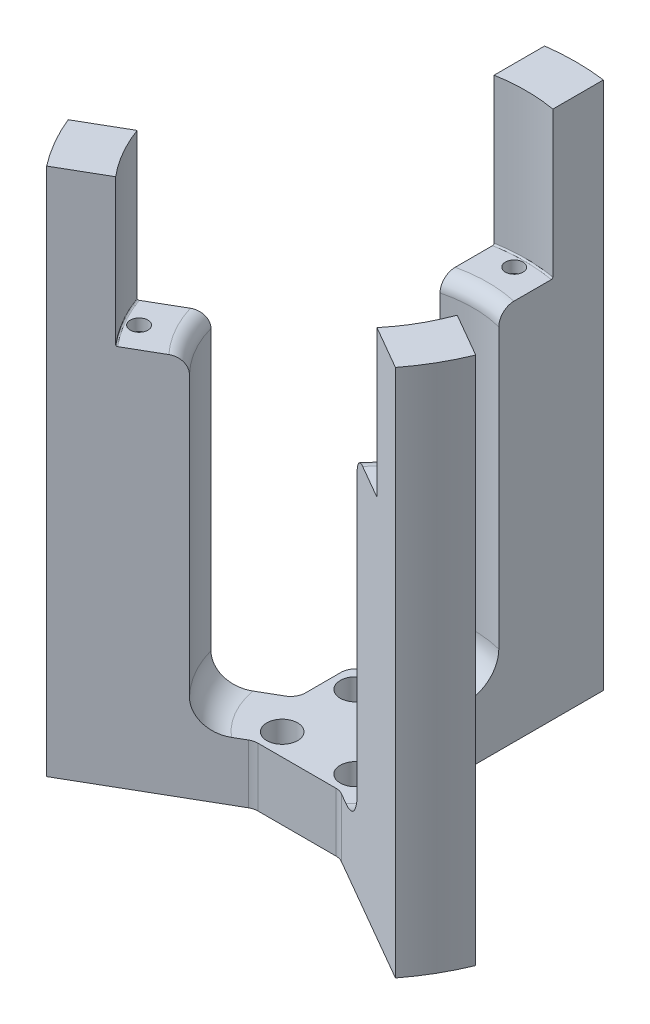
SolidWorks part; units mm, degrees
ref_plane "Front Plane" through (0, 0, 0) normal (0, 0, 1) x (1, 0, 0)
ref_plane "Top Plane" through (0, 0, 0) normal (0, 1, 0) x (1, 0, 0)
ref_plane "Right Plane" through (0, 0, 0) normal (1, 0, 0) x (0, 0, -1)
sketch "Sketch1" plane through (0, 0, 0) normal (0, 1, 0) x (1, 0, 0)
  line L0 (-10, 0) -> (-10, 74.3303)
  line L1 (10, 74.3303) -> (10, 0)
  arc A0 (-10, 0) -> (10, 0) centre (0, 0) ccw
  arc A1 (-10, 74.3303) -> (10, 74.3303) centre (0, 0) cw
  dimension "D1" = 75
  dimension "D2" = 20
extrude "Boss-Extrude1" add sketch "Sketch1" along normal blind 20
sketch "Sketch2" plane through (0, 20, 0) normal (0, 1, 0) x (1, 0, 0)
  line L0 (-10, 74.3303) -> (-10, 0) construction
  line L1 (10, 0) -> (10, 74.3303) construction
  line L2 (-10, 74.3303) -> (-10, 38.7298)
  line L3 (10, 74.3303) -> (10, 38.7298)
  arc A0 (-10, 38.7298) -> (10, 38.7298) centre (0, 0) cw
  arc A1 (10, 74.3303) -> (-10, 74.3303) centre (0, 0) ccw construction
  arc A2 (10, 74.3303) -> (-10, 74.3303) centre (0, 0) ccw
  dimension "D1" = 40
extrude "Boss-Extrude2" add sketch "Sketch2" along normal blind 160
sketch "Sketch3" plane through (0, 180, 0) normal (0, 1, 0) x (1, 0, 0)
  circle A0 centre (0, 0) radius 58
  dimension "D1" = 116
extrude "Cut-Extrude1" cut sketch "Sketch3" against normal blind 50
sketch "Sketch4" plane through (0, 130, 0) normal (0, 1, 0) x (1, 0, 0)
  circle A0 centre (0, 0) radius 53.975 construction
  circle A1 centre (0, 53.975) radius 3
  dimension "D1" = 107.95
  dimension "D2" = 6
extrude "Cut-Extrude2" cut sketch "Sketch4" against normal blind 4
pattern_circular "CirPattern1" count 3 over 360 about axis through (0, 0, 0) along (0, 1, 0) of "Boss-Extrude1", "Boss-Extrude2", "Cut-Extrude1", "Cut-Extrude2"
sketch "Sketch6" plane through (0, 0, 0) normal (0, 1, 0) x (1, 0, 0)
  line L1 (15, -20) -> (-15, -20)
  line L2 (20, -15) -> (20, 15)
  line L3 (15, 20) -> (-15, 20)
  line L4 (-20, -15) -> (-20, 15)
  line L5 (20, -20) -> (-20, 20) construction
  line L6 (20, 20) -> (-20, -20) construction
  arc A0 (-15, 20) -> (-20, 15) centre (-15, 15) ccw
  arc A1 (20, 15) -> (15, 20) centre (15, 15) ccw
  arc A2 (15, -20) -> (20, -15) centre (15, -15) ccw
  arc A3 (-15, -20) -> (-20, -15) centre (-15, -15) cw
  point P0 (0, 0)
  dimension "D2" = 5
  dimension "D1" = 40
extrude "Boss-Extrude3" add sketch "Sketch6" along normal up to surface (20 mm away) up to face at (0, 20, 0)
sketch "Sketch5" plane through (0, 20, 0) normal (0, 1, 0) x (1, 0, 0)
  line L1 (-12.5, -12.5) -> (12.5, -12.5) construction
  line L2 (-12.5, -12.5) -> (-12.5, 12.5) construction
  line L3 (-12.5, 12.5) -> (12.5, 12.5) construction
  line L4 (12.5, -12.5) -> (12.5, 12.5) construction
  line L5 (-12.5, -12.5) -> (12.5, 12.5) construction
  line L6 (-12.5, 12.5) -> (12.5, -12.5) construction
  circle A0 centre (-12.5, 12.5) radius 3.2
  circle A1 centre (12.5, 12.5) radius 3.2
  circle A2 centre (-12.5, -12.5) radius 3.2
  circle A3 centre (12.5, -12.5) radius 3.2
  point P0 (0, 0)
  dimension "D2" = 6.4
  dimension "D1" = 25
extrude "Cut-Extrude3" cut sketch "Sketch5" against normal through all
fillet "Fillet1" radius 10 3 edges at (0, 20, -40) (34.641, 20, 20) (-34.641, 20, 20)
fillet "Fillet2" radius 5 13 edges at (34.641, 130, 20) (-14.641, 10, 20) (-20, 10, 0) (20, 10, 0) (12.5, 0, -20) (10, 10, -20) (-10, 10, -20) (-12.5, 0, -20) (14.641, 10, 20) (12.5, 20, -20) (-12.5, 20, -20) (0, 130, -40) (-34.641, 130, 20)
fillet "Fillet4" radius 0.5 3 edges at (50.2295, 130, 29) (-50.2295, 130, 29) (0, 130, -58)
sketch "Sketch7" plane through (0, 20, 0) normal (0, 1, 0) x (1, 0, 0)
  circle A0 centre (-12.5, 12.5) radius 5.25
  circle A1 centre (12.5, 12.5) radius 5.25
  circle A2 centre (12.5, -12.5) radius 5.25
  circle A3 centre (-12.5, -12.5) radius 5.25
  dimension "D1" = 10.5
extrude "Cut-Extrude4" cut sketch "Sketch7" against normal blind 10
